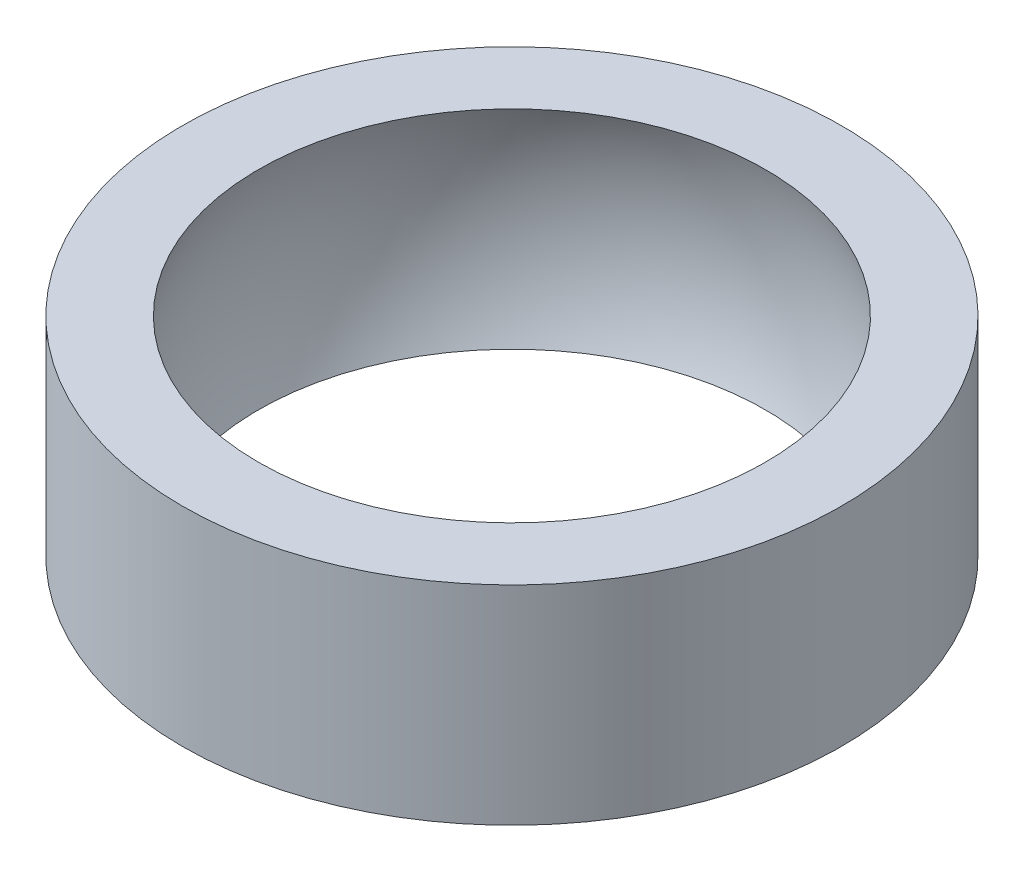
SolidWorks part; units mm, degrees
ref_plane "前视基准面" through (0, 0, 0) normal (0, 0, 1) x (1, 0, 0)
ref_plane "上视基准面" through (0, 0, 0) normal (0, 1, 0) x (1, 0, 0)
ref_plane "右视基准面" through (0, 0, 0) normal (1, 0, 0) x (0, 0, -1)
other "Configuration Table"
sketch "草图1" plane through (0, 0, 0) normal (0, 1, 0) x (1, 0, 0)
  circle A0 centre (0, 0) radius 9.5
  dimension "D1" = 19
extrude "凸台-拉伸1" add sketch "草图1" along normal mid plane 6
ref_plane "基准面1" through (0, 0, 0) normal (0, 1, 0) x (1, 0, 0)
sketch "草图2" plane through (0, 0, 0) normal (0, 1, 0) x (1, 0, 0)
  line L0 (-7.9, 0) -> (7.9, 0)
  circle A0 centre (0, 0) radius 7.9
  dimension "D1" = 15.8
revolve "切除-旋转9" cut sketch "草图2" angle 360 about L0 region at (0, 0, 3.3529)
